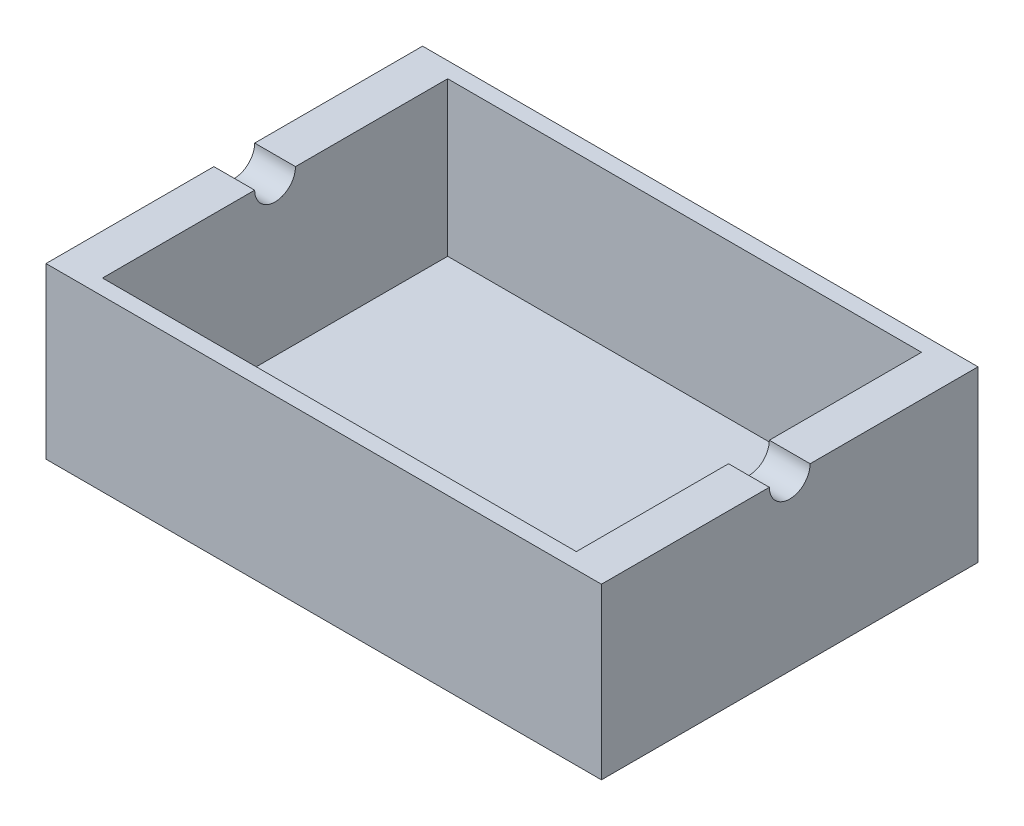
SolidWorks part; units mm, degrees
ref_plane "Alzado" through (0, 0, 0) normal (0, 0, 1) x (1, 0, 0)
ref_plane "Planta" through (0, 0, 0) normal (0, 1, 0) x (1, 0, 0)
ref_plane "Vista lateral" through (0, 0, 0) normal (1, 0, 0) x (0, 0, -1)
sketch "Croquis1" plane through (0, 0, 0) normal (0, 1, 0) x (1, 0, 0)
  line L1 (-30.2, -22) -> (30.2, -22)
  line L2 (-30.2, -22) -> (-30.2, 22)
  line L3 (-30.2, 22) -> (30.2, 22)
  line L4 (30.2, -22) -> (30.2, 22)
  line L5 (-30.2, -22) -> (30.2, 22) construction
  line L6 (-30.2, 22) -> (30.2, -22) construction
  line L7 (-35.4, -24) -> (35.4, -24)
  line L8 (-35.4, -24) -> (-35.4, 24)
  line L9 (-35.4, 24) -> (35.4, 24)
  line L10 (35.4, -24) -> (35.4, 24)
  line L11 (-35.4, -24) -> (35.4, 24) construction
  line L12 (-35.4, 24) -> (35.4, -24) construction
  point P0 (0, 0)
  point P6 (0, 0)
  dimension "D1" = 60.4
  dimension "D2" = 44
  dimension "D3" = 2
  dimension "D4" = 5.2
extrude "Saliente-Extruir1" add sketch "Croquis1" along normal blind 19.6
extrude "Saliente-Extruir2" add sketch "Croquis1<2>" against normal blind 2 contours L7 L10 L9 L8 L4 L1 L2 L3 | L1 L4 L3 L2 region at (0, 0, 0) region at (-34.5446, 0, 0)
sketch "Croquis1<2>" plane through (0, 0, 0) normal (0, 1, 0) x (1, 0, 0) same geometry as "Croquis1"
ref_plane "Plano1" through (35.4, 0, 0) normal (1, 0, 0) x (0, 0, -1)
sketch "Croquis2" plane through (35.4, 0, 0) normal (1, 0, 0) x (0, 0, -1)
  line L0 (-24, 19.6) -> (24, 19.6) construction
  line L1 (-2.6, 19.6) -> (2.6, 19.6)
  arc A0 (-2.6, 19.6) -> (2.6, 19.6) centre (0, 19.6) ccw
  dimension "D1" = 2.6
extrude "Cortar-Extruir1" cut sketch "Croquis2" against normal up to surface (70.8 mm away) up to face at (-35.4, 8.8, 0)
